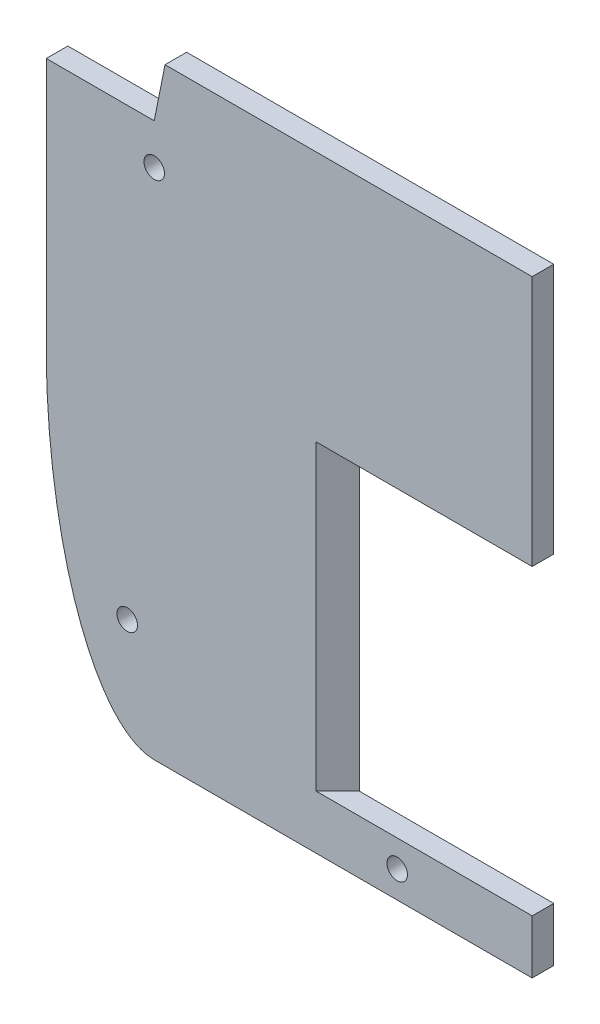
SolidWorks part; units mm, degrees
ref_plane "Front Plane" through (0, 0, 0) normal (0, 0, 1) x (1, 0, 0)
ref_plane "Top Plane" through (0, 0, 0) normal (0, 1, 0) x (1, 0, 0)
ref_plane "Right Plane" through (0, 0, 0) normal (1, 0, 0) x (0, 0, -1)
sketch "Sketch2" plane through (0, 0, 0) normal (0, 0, 1) x (1, 0, 0)
  line L1 (0, 0) -> (114.3, 0)
  line L2 (0, 0) -> (0, 142.875)
  line L3 (0, 142.875) -> (114.3, 142.875)
  line L4 (114.3, 0) -> (114.3, 142.875)
  dimension "D1" = 114.3
  dimension "D2" = 142.875
extrude "Boss-Extrude2" add sketch "Sketch2" along normal blind 30.48 contours L3 L4 L1 L2
fillet "Fillet1" radius 71.501 1 edges at (0, 0, 15.24) second distance 25.4 first distance on face at (0, 71.4375, 15.24)
sketch "Sketch3" plane through (0, 142.875, 0) normal (0, 1, 0) x (1, 0, 0)
  line L0 (0, -30.48) -> (114.3, -30.48) construction
  line L1 (33.8666, -7.62) -> (33.8666, -27.94)
  line L10 (0, -30.48) -> (0, 0) construction
  line L13 (49.1066, -7.62) -> (49.1066, -27.94)
  arc A8 (33.8666, -7.62) -> (33.8666, -27.94) centre (41.4866, -17.78) ccw
  arc A9 (49.1066, -27.94) -> (49.1066, -7.62) centre (41.4866, -17.78) ccw
  dimension "D1" = 25.4
  dimension "D2" = 12.7
  dimension "D3" = 41.4866
  dimension "D5" = 7.62
  dimension "D6" = 7.62
extrude "Boss-Extrude3" add sketch "Sketch3" along normal blind 11.43
sketch "Sketch5" plane through (0, 0, 30.48) normal (0, 0, 1) x (1, 0, 0)
  line L0 (62.6533, 142.875) -> (77.8933, 142.875)
  line L1 (0, 142.875) -> (114.3, 142.875) construction
  line L2 (0, 71.501) -> (0, 142.875) construction
  line L3 (114.3, 0) -> (114.3, 142.875) construction
  line L4 (91.44, 142.875) -> (106.68, 142.875)
  arc A0 (62.6533, 142.875) -> (77.8933, 142.875) centre (70.2733, 132.5567) ccw
  arc A1 (91.44, 142.875) -> (106.68, 142.875) centre (99.06, 132.5567) ccw
  dimension "D1" = 25.654
  dimension "D5" = 25.654
  dimension "D2" = 15.24
  dimension "D3" = 0
  dimension "D4" = 70.2733
  dimension "D6" = 15.24
  dimension "D7" = 15.24
extrude "Cut-Extrude2" cut sketch "Sketch5" against normal blind 25.4
fillet "Fillet2" radius 1.27 3 edges at (91.44, 142.875, 17.78) (77.8933, 142.875, 17.78) (62.6533, 142.875, 17.78)
sketch "Sketch7" plane through (0, 142.875, 0) normal (0, 1, 0) x (1, 0, 0)
  line L0 (0, -30.48) -> (59.4635, -30.48) construction
  line L1 (0, 0) -> (27.94, 0)
  line L2 (0, 0) -> (0, -30.48)
  line L3 (0, -30.48) -> (27.94, -30.48)
  line L4 (27.94, 0) -> (27.94, -30.48)
  dimension "D1" = 27.94
extrude "Cut-Extrude4" cut sketch "Sketch7" against normal blind 12.7
sketch "Sketch8" plane through (0, 130.175, 0) normal (0, 1, 0) x (1, 0, 0)
  line L6 (0, -30.48) -> (27.94, -30.48) construction
  line L7 (0, 0) -> (0, -30.48) construction
  line L8 (5.08, -7.62) -> (5.08, -27.94)
  line L9 (20.32, -7.62) -> (20.32, -27.94)
  arc A4 (5.08, -7.62) -> (5.08, -27.94) centre (12.7, -17.78) ccw
  arc A5 (20.32, -27.94) -> (20.32, -7.62) centre (12.7, -17.78) ccw
  dimension "D1" = 25.4
  dimension "D2" = 12.7
  dimension "D3" = 12.7
  dimension "D4" = 7.62
  dimension "D5" = 7.62
extrude "Boss-Extrude4" add sketch "Sketch8" along normal blind 11.43
sketch "Sketch10" plane through (0, 0, 30.48) normal (0, 0, 1) x (1, 0, 0)
  line L0 (114.3, 0) -> (114.3, 142.875) construction
  line L1 (63.5, 109.855) -> (12.7, 109.855)
  line L3 (63.5, 12.7) -> (38.1, 12.7)
  line L4 (12.7, 109.855) -> (12.7, 61.2775)
  line L5 (0, 71.501) -> (0, 130.175) construction
  line L6 (25.4, 0) -> (114.3, 0) construction
  line L7 (27.94, 142.875) -> (59.4635, 142.875) construction
  line L8 (12.7, 61.2775) -> (38.1, 12.7)
  line L14 (63.5, 94.615) -> (63.5, 12.7)
  line L15 (63.5, 109.855) -> (106.68, 109.855)
  line L17 (63.5, 94.615) -> (106.68, 94.615)
  line L18 (106.68, 109.855) -> (106.68, 94.615)
  dimension "D1" = 7.62
  dimension "D2" = 12.7
  dimension "D3" = 12.7
  dimension "D4" = 33.02
  dimension "D5" = 15.24
extrude "Cut-Extrude6" cut sketch "Sketch10" against normal blind 25.4
sketch "Sketch11" plane through (49.1066, 0, 0) normal (-1, 0, 0) x (0, 0, 1)
  line L0 (7.62, 154.305) -> (27.94, 154.305) construction
  line L1 (27.94, 154.305) -> (27.94, 142.875) construction
  line L2 (27.94, 154.305) -> (7.62, 154.305) construction
  line L3 (22.0449, 151.9849) -> (27.94, 142.875)
  line L4 (27.94, 142.875) -> (27.94, 154.305)
  line L5 (27.94, 154.305) -> (17.78, 154.305)
  circle A0 centre (17.78, 149.225) radius 3.175
  arc A1 (17.78, 154.305) -> (22.0449, 151.9849) centre (17.78, 149.225) cw
  dimension "D2" = 6.35
  dimension "D1" = 5.08
  dimension "D3" = 10.16
extrude "Cut-Extrude7" cut sketch "Sketch11" against normal through all both and the other way through all
sketch "Sketch12" plane through (20.32, 0, 0) normal (-1, 0, 0) x (0, 0, 1)
  line L0 (27.94, 141.605) -> (27.94, 130.175) construction
  line L1 (7.62, 141.605) -> (27.94, 141.605) construction
  line L2 (27.94, 141.605) -> (7.62, 141.605) construction
  line L3 (22.0449, 139.2849) -> (27.94, 130.175)
  line L4 (27.94, 130.175) -> (27.94, 141.605)
  line L5 (27.94, 141.605) -> (17.78, 141.605)
  circle A0 centre (17.78, 136.525) radius 3.175
  arc A1 (17.78, 141.605) -> (22.0449, 139.2849) centre (17.78, 136.525) cw
  dimension "D1" = 6.35
  dimension "D2" = 10.16
  dimension "D3" = 5.08
extrude "Cut-Extrude8" cut sketch "Sketch12" against normal up to surface (7.62 mm away) and the other way through all up to face at (27.94, 136.525, 15.24)
chamfer "Chamfer1" distance 12.7 distance2 2.54 1 edges at (27.94, 130.175, 15.24) first distance on face at (27.94, 136.525, 15.24)
sketch "Sketch13" plane through (0, 0, 30.48) normal (0, 0, 1) x (1, 0, 0)
  line L1 (114.3, 142.875) -> (106.68, 142.875)
  line L2 (114.3, 142.875) -> (114.3, 137.795)
  line L3 (114.3, 137.795) -> (106.68, 137.795)
  line L4 (106.68, 142.875) -> (106.68, 137.795)
  dimension "D1" = 7.62
  dimension "D2" = 5.08
extrude "Cut-Extrude9" cut sketch "Sketch13" against normal up to surface (25.4 mm away) up to face at (95.8158, 134.9459, 5.08)
fillet "Fillet4" radius 1.27 2 edges at (114.3, 137.795, 17.78) (110.7686, 137.795, 17.78)
sketch "Sketch14" plane through (0, 0, 30.48) normal (0, 0, 1) x (1, 0, 0)
  line L0 (114.3, 0) -> (114.3, 136.525) construction
  line L1 (114.3, 12.7) -> (81.28, 12.7)
  line L2 (114.3, 12.7) -> (114.3, 83.82)
  line L3 (114.3, 83.82) -> (81.28, 83.82)
  line L4 (81.28, 12.7) -> (81.28, 26.67)
  line L5 (25.4, 0) -> (114.3, 0) construction
  line L6 (81.28, 69.85) -> (81.28, 83.82)
  line L7 (81.28, 69.85) -> (111.76, 69.85)
  line L9 (81.28, 26.67) -> (111.76, 26.67)
  line L10 (111.76, 69.85) -> (111.76, 26.67)
  dimension "D1" = 12.7
  dimension "D2" = 71.12
  dimension "D3" = 33.02
  dimension "D4" = 13.97
  dimension "D5" = 13.97
  dimension "D6" = 30.48
extrude "Cut-Extrude10" cut sketch "Sketch14" against normal through all
chamfer "Chamfer2" distance 12.7 distance2 12.7 2 edges at (81.28, 19.685, 30.48) (81.28, 76.835, 30.48)
sketch "Sketch15" plane through (0, 0, 0) normal (0, -1, 0) x (1, 0, 0)
  line L0 (114.3, 30.48) -> (114.3, 0) construction
  line L1 (25.4, 30.48) -> (114.3, 30.48) construction
  circle A0 centre (99.06, 17.78) radius 3.175
  dimension "D1" = 6.35
  dimension "D2" = 15.24
  dimension "D3" = 12.7
extrude "Cut-Extrude11" cut sketch "Sketch15" against normal up to surface (109.855 mm away) up to face at (59.69, 109.855, 17.78)
sketch "Sketch16" plane through (0, 141.605, 0) normal (0, 1, 0) x (1, 0, 0)
  line L0 (0.407, -14.5906) -> (5.08, -14.605)
  line L1 (5.08, -14.605) -> (5.08, -7.62)
  line L2 (20.32, -14.605) -> (24.9967, -14.605)
  line L3 (20.32, -7.62) -> (20.32, -17.78) construction
  line L4 (20.32, -7.62) -> (20.32, -14.605)
  arc A0 (24.9967, -14.605) -> (20.32, -7.62) centre (12.7, -17.78) ccw
  arc A1 (5.08, -7.62) -> (0.407, -14.5906) centre (12.7, -17.78) ccw
extrude "Boss-Extrude5" add sketch "Sketch16" along normal blind 1.27
chamfer "Chamfer3" distance 1.27 angle 45 2 edges at (22.6584, 142.875, 14.605) (2.7435, 142.875, 14.5978)
sketch "Sketch17" plane through (0, 154.305, 0) normal (0, 1, 0) x (1, 0, 0)
  line L0 (29.1505, -14.7614) -> (33.8666, -14.7614)
  line L1 (33.8666, -17.78) -> (33.8666, -7.62) construction
  line L2 (33.8666, -14.7614) -> (33.8666, -7.62)
  line L4 (49.1066, -14.7614) -> (53.8226, -14.7614)
  line L5 (49.1066, -7.62) -> (49.1066, -17.78) construction
  line L6 (49.1066, -7.62) -> (49.1066, -14.7614)
  arc A0 (33.8666, -7.62) -> (29.1505, -14.7614) centre (41.4866, -17.78) ccw
  arc A1 (53.8226, -14.7614) -> (49.1066, -7.62) centre (41.4866, -17.78) ccw
extrude "Boss-Extrude6" add sketch "Sketch17" along normal blind 1.27
chamfer "Chamfer4" distance 1.27 angle 45 2 edges at (51.4646, 155.575, 14.7614) (31.5086, 155.575, 14.7614)
fillet "Fillet5" radius 15.24 1 edges at (111.76, 48.26, 30.48)
sketch "Sketch19" plane through (0, 0, 30.48) normal (0, 0, 1) x (1, 0, 0)
  line L0 (111.76, 69.85) -> (111.76, 26.67) construction
  line L1 (81.28, 52.07) -> (111.76, 52.07)
  line L3 (81.28, 57.15) -> (111.76, 57.15)
  line L4 (111.76, 52.07) -> (111.76, 57.15)
  line L5 (81.28, 52.07) -> (111.76, 57.15) construction
  line L6 (81.28, 57.15) -> (111.76, 52.07) construction
  line L7 (68.58, 69.85) -> (96.52, 69.85) construction
  line L9 (81.28, 57.15) -> (69.85, 57.15)
  line L11 (81.28, 52.07) -> (69.85, 52.07)
  line L12 (69.85, 57.15) -> (69.85, 52.07)
  point P0 (96.52, 54.61)
  dimension "D1" = 15.24
  dimension "D2" = 5.08
  dimension "D3" = 12.7
  dimension "D4" = 11.43
extrude "Cut-Extrude12" cut sketch "Sketch19" against normal blind 16.51
sketch "Sketch20" plane through (63.5, 0, 0) normal (-1, 0, 0) x (0, 0, 1)
  line L0 (30.48, 12.7) -> (30.48, 94.615) construction
  line L1 (17.78, 40.64) -> (20.32, 40.64)
  line L2 (17.78, 40.64) -> (17.78, 38.1)
  line L3 (17.78, 38.1) -> (20.32, 38.1)
  line L4 (20.32, 40.64) -> (20.32, 38.1)
  line L5 (5.08, 12.7) -> (30.48, 12.7) construction
  dimension "D1" = 2.54
  dimension "D2" = 2.54
  dimension "D3" = 12.7
  dimension "D4" = 25.4
extrude "Cut-Extrude13" cut sketch "Sketch20" against normal through all
fillet "Fillet6" radius 1.27 1 edges at (63.5, 38.1, 19.05)
ref_plane "Plane1" through (0, 0, 17.78) normal (0, 0, 1) x (1, 0, 0)
sketch "Sketch21" plane through (0, 0, 17.78) normal (0, 0, 1) x (1, 0, 0)
  line L0 (12.7, 109.855) -> (10.4859, 130.175)
  line L1 (0, 130.175) -> (25.4, 130.175) construction
  line L2 (10.4859, 130.175) -> (15.5659, 130.175)
  line L3 (15.5659, 130.175) -> (17.78, 109.855)
  line L4 (106.68, 109.855) -> (12.7, 109.855) construction
  line L5 (17.78, 109.855) -> (12.7, 109.855)
  line L6 (55.4297, 142.875) -> (50.8604, 121.6537)
  line L7 (27.94, 142.875) -> (59.4635, 142.875) construction
  line L8 (38.9466, 142.875) -> (44.0266, 142.875)
  line L9 (38.9466, 142.875) -> (38.9466, 109.855)
  line L10 (38.9466, 109.855) -> (44.0266, 109.855)
  line L11 (44.0266, 142.875) -> (44.0266, 109.855)
  line L12 (33.8666, 151.9849) -> (33.8666, 142.875) construction
  line L13 (50.8604, 121.6537) -> (50.8604, 109.855)
  line L14 (66.8866, 120.1849) -> (71.9666, 120.1849)
  line L15 (66.8866, 120.1849) -> (66.8866, 109.855)
  line L16 (66.8866, 109.855) -> (71.9666, 109.855)
  line L17 (71.9666, 120.1849) -> (71.9666, 109.855)
  line L18 (96.0966, 120.0767) -> (101.1766, 120.0767)
  line L19 (96.0966, 120.0767) -> (96.0966, 109.855)
  line L20 (96.0966, 109.855) -> (101.1766, 109.855)
  line L21 (101.1766, 120.0767) -> (101.1766, 109.855)
  line L22 (50.8604, 109.855) -> (52.4497, 109.855)
  line L23 (52.4497, 109.855) -> (52.4497, 121.6537)
  line L24 (52.4497, 121.6537) -> (57.0191, 142.875)
  line L25 (57.0191, 142.875) -> (55.4297, 142.875)
  line L36 (106.68, 94.615) -> (106.68, 109.855) construction
  line L37 (106.68, 103.1464) -> (114.3, 103.1464)
  line L38 (106.68, 103.1464) -> (106.68, 101.7444)
  line L39 (106.68, 101.7444) -> (114.3, 101.7444)
  line L40 (114.3, 103.1464) -> (114.3, 101.7444)
  line L41 (114.3, 83.82) -> (114.3, 136.525) construction
  line L42 (81.0832, 142.875) -> (88.2501, 142.875) construction
  line L43 (83.8937, 142.875) -> (85.379, 142.875)
  line L44 (83.8937, 142.875) -> (83.8937, 109.855)
  line L45 (83.8937, 109.855) -> (85.379, 109.855)
  line L46 (85.379, 142.875) -> (85.379, 109.855)
  arc A0 (60.4373, 140.7898) -> (80.1093, 140.7898) centre (70.2733, 132.5567) ccw construction
  arc A1 (89.224, 140.7898) -> (111.3683, 136.1675) centre (99.06, 132.5567) ccw construction
  point P9 (13.0259, 130.175)
  dimension "D1" = 5.08
  dimension "D2" = 2.5251
  dimension "D3" = 5.08
  dimension "D4" = 5.08
  dimension "D5" = 5.08
  dimension "D6" = 22.86
  dimension "D7" = 5.08
  dimension "D8" = 24.13
extrude "Cut-Extrude14" cut sketch "Sketch21" against normal blind 1.27 and the other way blind 1.27
fillet "Fillet7" radius 11.43 1 edges at (63.5, 94.615, 17.78)
sketch "Sketch22" plane through (0, 12.7, 0) normal (0, 1, 0) x (1, 0, 0)
  line L0 (38.1, -5.08) -> (38.1, -30.48) construction
  circle A0 centre (43.18, -11.9083) radius 1.27
  circle A1 centre (48.26, -11.9083) radius 1.27
  circle A2 centre (53.34, -11.9083) radius 1.27
  circle A3 centre (58.42, -11.9083) radius 1.27
  circle A4 centre (43.18, -22.0683) radius 1.27
  circle A5 centre (48.26, -22.0683) radius 1.27
  circle A6 centre (53.34, -22.0683) radius 1.27
  circle A7 centre (58.42, -22.0683) radius 1.27
  dimension "D1" = 2.54
  dimension "D2" = 2.54
  dimension "D3" = 2.54
  dimension "D4" = 2.54
  dimension "D5" = 2.54
  dimension "D6" = 2.54
  dimension "D7" = 2.54
  dimension "D8" = 2.54
  dimension "D9" = 10.16
  dimension "D10" = 10.16
  dimension "D11" = 10.16
  dimension "D12" = 10.16
  dimension "D13" = 5.08
  dimension "D14" = 5.08
  dimension "D15" = 5.08
  dimension "D16" = 5.08
extrude "Cut-Extrude15" cut sketch "Sketch22" against normal up to surface (12.7 mm away) up to face at (99.06, 0, 14.605)
sketch "Sketch24" plane through (0, 0, 30.48) normal (0, 0, 1) x (1, 0, 0)
  line L1 (114.3, 0) -> (-6.2245, 0)
  line L2 (114.3, 0) -> (114.3, 158.4155)
  line L3 (114.3, 158.4155) -> (-6.2245, 158.4155)
  line L4 (-6.2245, 0) -> (-6.2245, 158.4155)
extrude "Cut-Extrude17" cut sketch "Sketch24" against normal blind 25.4
sketch "Sketch25" plane through (0, 0, 5.08) normal (0, 0, 1) x (1, 0, 0)
  line L1 (114.3, 83.82) -> (68.58, 83.82)
  line L2 (114.3, 83.82) -> (114.3, 12.6603)
  line L3 (114.3, 12.6603) -> (68.58, 12.6603)
  line L4 (68.58, 83.82) -> (68.58, 12.6603)
  dimension "D1" = 45.72
extrude "Cut-Extrude18" cut sketch "Sketch25" against normal through all
chamfer "Chamfer5" distance 5.08 angle 45 1 edges at (68.58, 48.2401, 5.08)
sketch "Sketch27" plane through (0, 0, 5.08) normal (0, 0, 1) x (1, 0, 0)
  line L0 (0, 71.501) -> (0, 130.175) construction
  line L1 (25.4, 0) -> (114.3, 0) construction
  circle A0 centre (25.4, 120.65) radius 2.413
  circle A1 centre (19.05, 25.4) radius 2.413
  circle A2 centre (82.55, 6.35) radius 2.413
  point P10 (0, 0)
  dimension "D1" = 4.826
  dimension "D2" = 4.826
  dimension "D3" = 4.826
  dimension "D4" = 25.4
  dimension "D5" = 120.65
  dimension "D6" = 19.05
  dimension "D7" = 25.4
  dimension "D8" = 82.55
  dimension "D9" = 6.35
extrude "Cut-Extrude20" cut sketch "Sketch27" against normal through all
